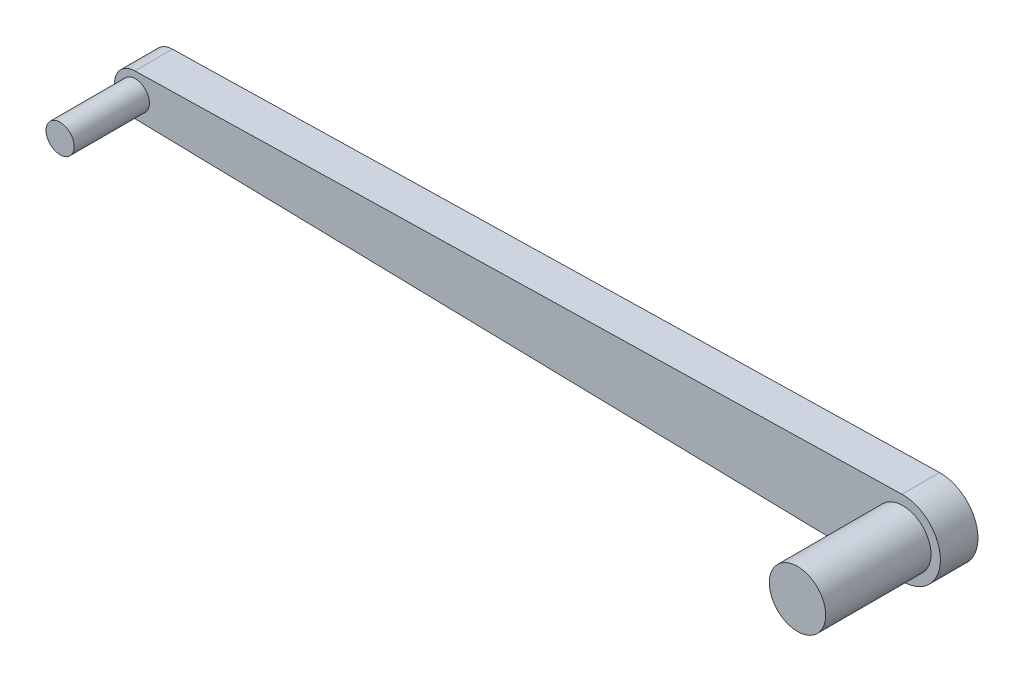
SolidWorks part; units mm, degrees
ref_plane "Front Plane" through (0, 0, 0) normal (0, 0, 1) x (1, 0, 0)
ref_plane "Top Plane" through (0, 0, 0) normal (0, 1, 0) x (1, 0, 0)
ref_plane "Right Plane" through (0, 0, 0) normal (1, 0, 0) x (0, 0, -1)
sketch "Sketch1" plane through (0, 0, 0) normal (0, 0, 1) x (1, 0, 0)
  line L0 (-10.205, 0) -> (10.205, 0) construction
  line L1 (-10.2171, 0.5499) -> (10.183, 0.9998)
  line L2 (-10.2171, -0.5499) -> (10.183, -0.9998)
  circle A0 centre (-10.205, 0) radius 0.375
  arc A1 (-10.2171, 0.5499) -> (-10.2171, -0.5499) centre (-10.205, 0) ccw
  circle A2 centre (10.205, 0) radius 0.75
  arc A3 (10.183, -0.9998) -> (10.183, 0.9998) centre (10.205, 0) ccw
  point P4 (0, 0)
  dimension "D1" = 0.75
  dimension "D2" = 1.1
  dimension "D3" = 1.5
  dimension "D4" = 2
  dimension "D5" = 20.41
extrude "Boss-Extrude1" add sketch "Sketch1" along normal mid plane 1
extrude "Boss-Extrude2" add sketch "Sketch1<2>" along normal blind 2.5 contours A0 region at (-10.205, 0, 0)
sketch "Sketch1<2>" plane through (0, 0, 0) normal (0, 0, 1) x (1, 0, 0) same geometry as "Sketch1"
extrude "Boss-Extrude3" add sketch "Sketch1<3>" along normal blind 3.3 contours A2 region at (10.205, 0, 0)
sketch "Sketch1<3>" plane through (0, 0, 0) normal (0, 0, 1) x (1, 0, 0) same geometry as "Sketch1"
sketch "Sketch2" plane through (0, 0, 0) normal (0, 0, -1) x (-1, 0, 0)
  circle A1 centre (10.205, 0) radius 0.375
  circle A2 centre (10.205, 0) radius 0.375
  circle A3 centre (-10.205, 0) radius 0.75
  circle A4 centre (-10.205, 0) radius 0.75
  dimension "D1" = 0
  dimension "D2" = 0
extrude "Boss-Extrude4" add sketch "Sketch2" along normal up to surface (0.5 mm away) up to face at (0.104, 0, -0.5)
